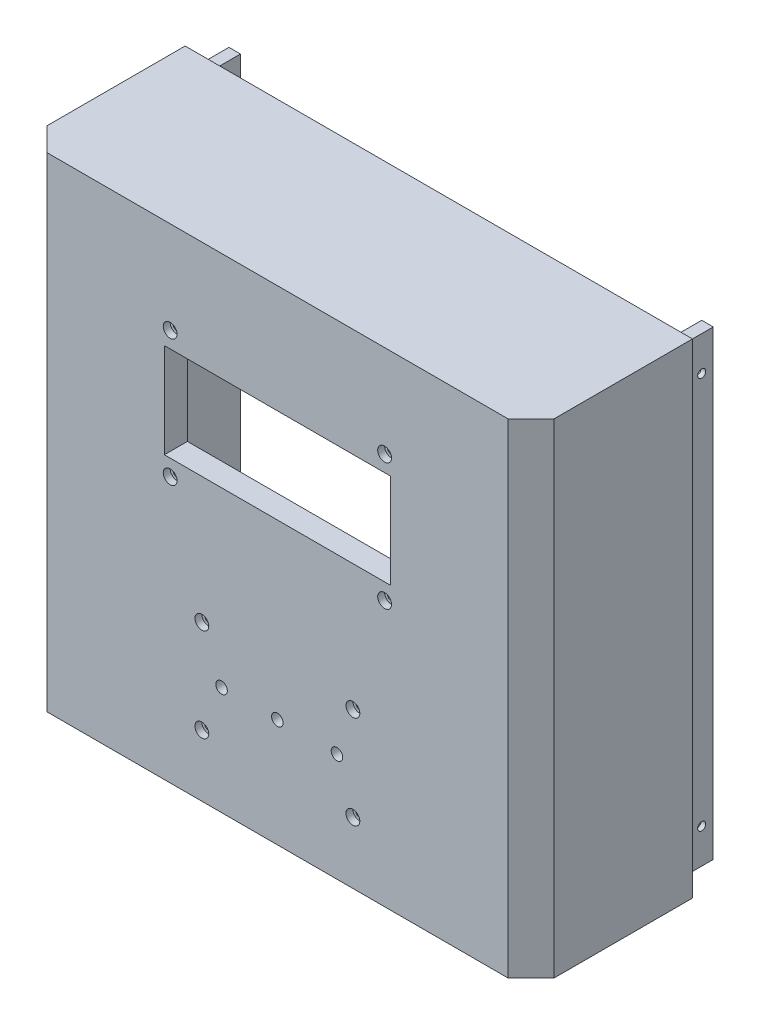
SolidWorks part; units mm, degrees
ref_plane "Płaszczyzna przednia" through (0, 0, 0) normal (0, 0, 1) x (1, 0, 0)
ref_plane "Płaszczyzna górna" through (0, 0, 0) normal (0, 1, 0) x (1, 0, 0)
ref_plane "Płaszczyzna prawa" through (0, 0, 0) normal (1, 0, 0) x (0, 0, -1)
sketch "Sketch1" plane through (0, 0, 0) normal (0, 1, 0) x (1, 0, 0)
  line L0 (0, 0) -> (100, 0)
  line L1 (100, 0) -> (110, 10)
  line L2 (110, 10) -> (110, 70)
  line L3 (110, 70) -> (100, 70)
  line L4 (100, 70) -> (100, 10)
  line L6 (100, 10) -> (0, 10)
  line L7 (0, 10) -> (0, 0)
  point P3 (10.8903, 5.2532)
  point P7 (0, 0)
  point P10 (10.8903, 4.9068)
  point P11 (21.0635, 5)
  point P12 (21.1526, 5)
  dimension "D1" = 10
  dimension "D2" = 10
  dimension "D3" = 60
  dimension "D4" = 10
  dimension "D5" = 10
  dimension "D6" = 100
extrude "Boss-Extrude1" add sketch "Sketch1" along normal blind 200
mirror "Mirror1" about plane through (0, 0, 0) normal (1, 0, 0) of "Boss-Extrude1"
sketch "Sketch2" plane through (0, 0, 0) normal (1, 0, 0) x (0, 0, -1)
  line L0 (48, 0) -> (48, 95.5652) construction
  line L2 (0, 180) -> (91.2882, 180) construction
  line L4 (10, 200) -> (10, 0) construction
  line L7 (10, 200) -> (70, 200) construction
  line L8 (88.1265, 71) -> (-11.2927, 71) construction
  circle A0 centre (29.5, 103) radius 1.75
  circle A1 centre (38.5, 180) radius 1.75
  circle A2 centre (20.5, 180) radius 1.75
  dimension "D3" = 32
  dimension "D7" = 3.5
  dimension "D1" = 38
  dimension "D2" = 18.5
  dimension "D4" = 77
  dimension "D5" = 9.5
  dimension "D6" = 18
  dimension "D8" = 129
sketch "Sketch6" plane through (0, 0, 0) normal (0, 1, 0) x (1, 0, 0)
  line L0 (110, 70) -> (-110, 70)
  line L1 (-110, 70) -> (-110, 10)
  line L2 (-110, 10) -> (-100, 0)
  line L3 (-100, 0) -> (100, 0)
  line L4 (100, 0) -> (110, 10)
  line L5 (110, 10) -> (110, 70)
extrude "Boss-Extrude2" add sketch "Sketch6" against normal blind 5
extrude "Boss-Extrude3" add sketch "Sketch6<2>" along normal blind 5 from surface starting at face at (0, 200, -32)
sketch "Sketch6<2>" plane through (0, 0, 0) normal (0, 1, 0) x (1, 0, 0) same geometry as "Sketch6"
sketch "Sketch12" plane through (0, 0, 0) normal (0, 0, 1) x (1, 0, 0)
  line L1 (100, 200) -> (105, 200)
  line L2 (100, 200) -> (100, 0)
  line L3 (100, 0) -> (105, 0)
  line L4 (105, 200) -> (105, 0)
  line L5 (-100, 0) -> (-105, 0)
  line L6 (-100, 0) -> (-100, 200)
  line L7 (-100, 200) -> (-105, 200)
  line L8 (-105, 0) -> (-105, 200)
  dimension "D1" = 5
  dimension "D2" = 5
extrude "Boss-Extrude5" add sketch "Sketch12" against normal blind 14 from surface starting at face at (0, 100, -70)
sketch "Sketch13" plane through (0, 0, 0) normal (0, 0, 1) x (1, 0, 0)
  line L0 (100, 205) -> (-100, 205) construction
  line L1 (-46.5, 165) -> (46.5, 165) construction
  line L2 (-46.5, 165) -> (-46.5, 110) construction
  line L3 (-46.5, 110) -> (46.5, 110) construction
  line L4 (46.5, 165) -> (46.5, 110) construction
  line L5 (-46.5, 165) -> (46.5, 110) construction
  line L6 (-46.5, 110) -> (46.5, 165) construction
  line L7 (-49, 117) -> (49, 117)
  line L8 (-49, 117) -> (-49, 158)
  line L9 (-49, 158) -> (49, 158)
  line L10 (49, 117) -> (49, 158)
  line L11 (-49, 117) -> (49, 158) construction
  line L12 (-49, 158) -> (49, 117) construction
  line L13 (0, 137.5) -> (0, 33.2075) construction
  line L15 (-32.75, 41.9962) -> (32.75, 41.9962) construction
  line L16 (32.75, 62.2462) -> (-32.75, 62.2462) construction
  line L17 (32.75, 62.2462) -> (32.75, 21.7462) construction
  line L18 (32.75, 21.7462) -> (-32.75, 21.7462) construction
  line L19 (-32.75, 62.2462) -> (-32.75, 21.7462) construction
  line L20 (32.75, 62.2462) -> (-32.75, 21.7462) construction
  line L21 (32.75, 21.7462) -> (-32.75, 62.2462) construction
  circle A0 centre (-46.5, 165) radius 1.75
  circle A1 centre (46.5, 165) radius 1.75
  circle A2 centre (46.5, 110) radius 1.75
  circle A3 centre (-46.5, 110) radius 1.75
  circle A4 centre (32.75, 62.2462) radius 1.75
  circle A5 centre (-32.75, 62.2462) radius 1.75
  circle A6 centre (32.75, 21.7462) radius 1.75
  circle A7 centre (-32.75, 21.7462) radius 1.75
  circle A8 centre (25.8389, 41.9962) radius 2.5
  circle A9 centre (0, 41.9962) radius 2.5
  circle A10 centre (-24.2056, 41.9962) radius 2.5
  point P0 (0, 137.5)
  point P5 (0, 137.5)
  point P19 (0, 41.9962)
  point P36 (0, 41.9962)
  dimension "D5" = 3.5
  dimension "D9" = 3.5
  dimension "D10" = 3.5
  dimension "D11" = 3.5
  dimension "D12" = 3.5
  dimension "D13" = 5
  dimension "D1" = 93
  dimension "D2" = 98
  dimension "D3" = 55
  dimension "D4" = 41
  dimension "D6" = 40
  dimension "D7" = 65.5
  dimension "D8" = 40.5
extrude "Cut-Extrude7" cut sketch "Sketch13" against normal through all both and the other way through all
sketch "Sketch15" plane through (0, 0, 0) normal (0, 0, 1) x (1, 0, 0)
  circle A0 centre (-46.5, 165) radius 3
  circle A1 centre (46.5, 165) radius 3
  circle A2 centre (46.5, 110) radius 3
  circle A3 centre (-46.5, 110) radius 3
  dimension "D1" = 6
extrude "Cut-Extrude8" cut sketch "Sketch15" against normal blind 3 from surface starting at face at (44.75, 165, 0)
sketch "Sketch16" plane through (0, 0, 0) normal (1, 0, 0) x (0, 0, -1)
  line L0 (79, 204.548) -> (79, -4.9329) construction
  line L2 (10, 205) -> (70, 205) construction
  line L3 (70, -5) -> (10, -5) construction
  line L4 (70, 200) -> (70, 0) construction
  circle A0 centre (79, 185) radius 1.75
  circle A1 centre (79, 15) radius 1.75
  dimension "D2" = 3.5
  dimension "D1" = 9
  dimension "D3" = 20
  dimension "D4" = 20
extrude "Cut-Extrude9" cut sketch "Sketch16" against normal through all both and the other way through all
sketch "Sketch17" plane through (0, 0, 0) normal (1, 0, 0) x (0, 0, -1)
  line L1 (75.5359, 185) -> (77.2679, 182)
  line L2 (77.2679, 182) -> (80.7321, 182)
  line L3 (80.7321, 182) -> (82.4641, 185)
  line L4 (82.4641, 185) -> (80.7321, 188)
  line L5 (80.7321, 188) -> (77.2679, 188)
  line L6 (77.2679, 188) -> (75.5359, 185)
  line L7 (75.6907, 13.9761) -> (78.2321, 11.6221)
  line L8 (78.2321, 11.6221) -> (81.5414, 12.646)
  line L9 (81.5414, 12.646) -> (82.3093, 16.0239)
  line L10 (82.3093, 16.0239) -> (79.7679, 18.3779)
  line L11 (79.7679, 18.3779) -> (76.4586, 17.354)
  line L12 (76.4586, 17.354) -> (75.6907, 13.9761)
  circle A0 centre (79, 185) radius 3 construction
  circle A1 centre (79, 15) radius 3 construction
  point P10 (76.0746, 15.665)
  dimension "D1" = 6
  dimension "D2" = 6
extrude "Cut-Extrude10" cut sketch "Sketch17" against normal blind 3 from surface starting at face at (-100, 185, -80.75)
extrude "Cut-Extrude11" cut sketch "Sketch17<2>" along normal blind 3 from surface starting at face at (100, 185, -80.75)
sketch "Sketch17<2>" plane through (0, 0, 0) normal (1, 0, 0) x (0, 0, -1) same geometry as "Sketch17"
sketch "Sketch18" plane through (0, 0, 0) normal (0, 0, 1) x (1, 0, 0)
  circle A0 centre (32.75, 62.2462) radius 3
  circle A1 centre (-32.75, 62.2462) radius 3
  circle A2 centre (-32.75, 21.7462) radius 3
  circle A3 centre (32.75, 21.7462) radius 3
  point P11 (32.75, 21.7462)
  point P13 (33.117, 20.0351)
  dimension "D1" = 6
extrude "Cut-Extrude12" cut sketch "Sketch18" against normal blind 3 from surface starting at face at (-49.5, 110, 0)
